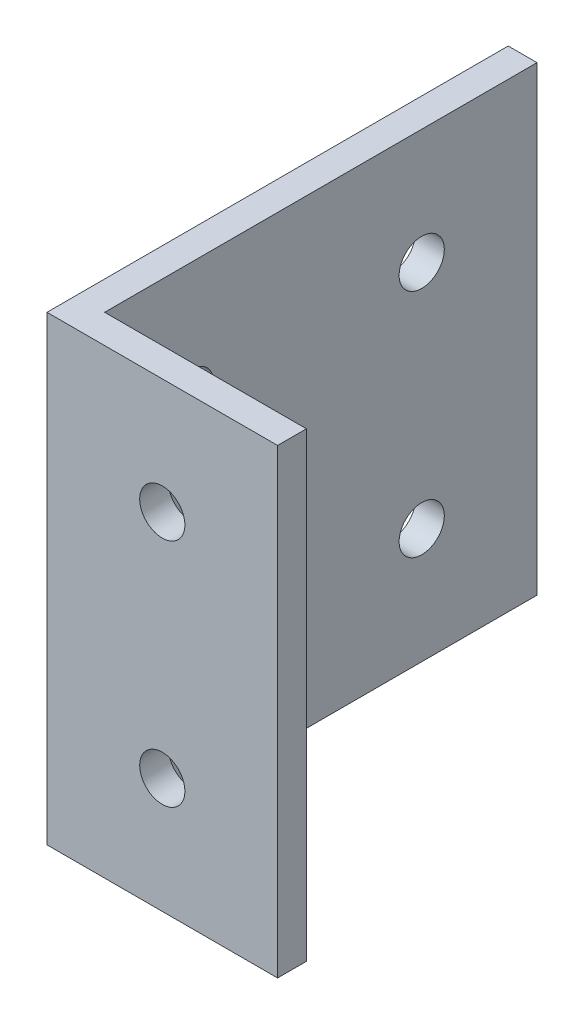
SolidWorks part; units mm, degrees
material "6061-T6 (SS)"
ref_plane "Front Plane" through (0, 0, 0) normal (0, 0, 1) x (1, 0, 0)
ref_plane "Top Plane" through (0, 0, 0) normal (0, 1, 0) x (1, 0, 0)
ref_plane "Right Plane" through (0, 0, 0) normal (1, 0, 0) x (0, 0, -1)
sketch "Sketch1" plane through (0, 0, 0) normal (0, 1, 0) x (1, 0, 0)
  line L0 (0, 0) -> (0, 50.8)
  line L1 (0, 50.8) -> (3.175, 50.8)
  line L2 (3.175, 50.8) -> (3.175, 3.175)
  line L3 (3.175, 3.175) -> (25.4, 3.175)
  line L4 (25.4, 3.175) -> (25.4, 0)
  line L5 (25.4, 0) -> (0, 0)
  dimension "D1" = 3.175
  dimension "D2" = 50.8
  dimension "D3" = 25.4
extrude "Boss-Extrude1" add sketch "Sketch1" along normal blind 50.8
sketch "Sketch2" plane through (3.175, 0, 0) normal (1, 0, 0) x (0, 0, -1)
  line L0 (50.8, 50.8) -> (50.8, 0) construction
  line L1 (3.175, 50.8) -> (50.8, 50.8) construction
  circle A0 centre (38.1, 38.1) radius 2.4892
  circle A1 centre (38.1, 12.7) radius 2.4892
  circle A2 centre (12.7, 12.7) radius 2.4892
  circle A3 centre (12.7, 38.1) radius 2.4892
  dimension "D1" = 4.9784
  dimension "D2" = 12.7
  dimension "D3" = 12.7
  dimension "D4" = 25.4
  dimension "D5" = 25.4
extrude "Cut-Extrude1" cut sketch "Sketch2" against normal through all
sketch "Sketch3" plane through (0, 0, -3.175) normal (0, 0, -1) x (-1, 0, 0)
  line L2 (-25.4, 0) -> (-3.175, 0) construction
  line L3 (-25.4, 50.8) -> (-25.4, 0) construction
  circle A0 centre (-12.7, 38.1) radius 2.4892
  circle A1 centre (-12.7, 12.7) radius 2.4892
  dimension "D1" = 4.9784
  dimension "D2" = 25.4
  dimension "D3" = 12.7
  dimension "D4" = 12.7
extrude "Cut-Extrude2" cut sketch "Sketch3" against normal through all
